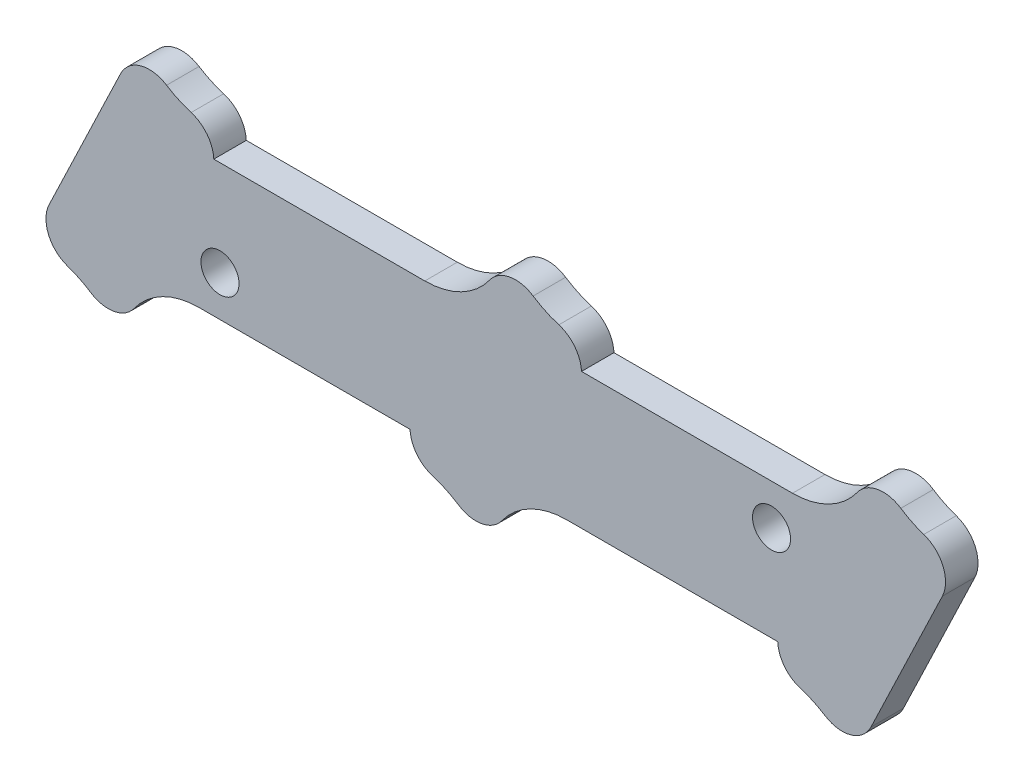
SolidWorks part; units mm, degrees
material "3003-H14"
ref_plane "X-Y Datum" through (0, 0, 0) normal (0, 0, 1) x (1, 0, 0)
ref_plane "X-Z Datum" through (0, 0, 0) normal (0, 1, 0) x (1, 0, 0)
ref_plane "Y-Z Datum" through (0, 0, 0) normal (1, 0, 0) x (0, 0, -1)
sketch "Sketch3" plane through (0, 0, 0) normal (0, 0, 1) x (1, 0, 0)
  line L0 (10.775, 10.775) -> (22.275, 34.775) construction
  line L1 (0, 0) -> (156.4633, 0) construction
  line L2 (0, 0) -> (0, 56.3098) construction
  line L3 (0, 56.3098) -> (156.4633, 56.3098) construction
  line L4 (156.4633, 0) -> (156.4633, 56.3098) construction
  line L5 (33.775, 10.775) -> (45.275, 34.775) construction
  line L6 (56.775, 10.775) -> (68.275, 34.775) construction
  line L7 (16.525, 22.775) -> (62.525, 22.775) construction
  line L8 (33.775, 10.775) -> (22.275, 34.775) construction
  line L9 (45.275, 34.775) -> (56.775, 10.775) construction
  line L10 (10.775, 10.775) -> (33.775, 10.775) construction
  line L11 (56.775, 10.775) -> (33.775, 10.775) construction
  line L12 (22.275, 34.775) -> (45.275, 34.775) construction
  line L13 (68.275, 34.775) -> (45.275, 34.775) construction
  line L14 (22.275, 34.775) -> (22.275, 10.775) construction
  line L15 (45.275, 10.775) -> (45.275, 34.775) construction
  line L16 (33.775, 10.775) -> (33.775, 34.775) construction
  line L17 (56.775, 34.775) -> (56.775, 10.775) construction
  line L18 (13.4804, 9.4786) -> (24.9804, 33.4786)
  line L19 (36.4804, 9.4786) -> (47.9804, 33.4786)
  line L20 (59.4804, 9.4786) -> (70.9804, 33.4786)
  line L21 (8.0696, 12.0714) -> (19.5696, 36.0714)
  line L22 (31.0696, 12.0714) -> (42.5696, 36.0714)
  line L23 (54.0696, 12.0714) -> (65.5696, 36.0714)
  line L24 (17.8152, 18.525) -> (57.1619, 18.525)
  line L25 (21.8881, 27.025) -> (61.2348, 27.025)
  line L26 (16.525, 27.025) -> (62.525, 27.025) construction
  line L27 (16.525, 18.525) -> (62.525, 18.525) construction
  line L48 (56.775, 10.775) -> (68.275, 10.775) construction
  line L49 (68.275, 10.775) -> (68.275, 34.775) construction
  circle A0 centre (10.775, 10.775) radius 10.775 construction
  circle A1 centre (33.775, 10.775) radius 10.775 construction
  circle A2 centre (22.275, 34.775) radius 10.775 construction
  circle A3 centre (45.275, 34.775) radius 10.775 construction
  circle A4 centre (68.275, 34.775) radius 10.775 construction
  circle A5 centre (56.775, 10.775) radius 10.775 construction
  circle A6 centre (10.775, 10.775) radius 4.7 construction
  circle A7 centre (33.775, 10.775) radius 4.7 construction
  circle A8 centre (56.775, 10.775) radius 4.7 construction
  circle A9 centre (68.275, 34.775) radius 4.7 construction
  circle A10 centre (45.275, 34.775) radius 4.7 construction
  circle A11 centre (22.275, 34.775) radius 4.7 construction
  circle A12 centre (22.275, 34.775) radius 6.2
  circle A13 centre (10.775, 10.775) radius 6.2
  circle A14 centre (33.775, 10.775) radius 6.2
  circle A15 centre (45.275, 34.775) radius 6.2
  circle A16 centre (68.275, 34.775) radius 6.2
  circle A17 centre (56.775, 10.775) radius 6.2
  circle A18 centre (125.775, 10.775) radius 10.775 construction
  circle A19 centre (102.775, 10.775) radius 10.775 construction
  circle A20 centre (79.775, 10.775) radius 10.775 construction
  circle A21 centre (91.275, 34.775) radius 10.775 construction
  circle A22 centre (114.275, 34.775) radius 10.775 construction
  circle A23 centre (137.275, 34.775) radius 10.775 construction
  dimension "D1" = 21.55
  dimension "D9" = 9.4
  dimension "D2" = 23
  dimension "D3" = 24
  dimension "D4" = 11.5
  dimension "D6" = 23
  dimension "D8" = 23
  dimension "D10" = 3
  dimension "D11" = 3
  dimension "D12" = 4.25
  dimension "D13" = 4.25
  dimension "D14" = 1.5
  dimension "D5" = 6
  dimension "D7" = 5
extrude "Boss-Extrude1" add sketch "Sketch3" along normal blind 2.032 contours L17 | L17 | L17 | L17 | L49 | A13 L18 A12 L21 | L25 L18 L24 L22 | L25 L22 L24 L19 | L25 L19 L24 L23 | A17 L20 A16 L23 | A14 L19 L24 L22 | A15 L22 L25 L19 region at (16.525, 22.775, 0) region at (28.025, 22.775, 0) region at (37.4592, 17.206, 0) region at (39.525, 22.775, 0) region at (41.5908, 28.344, 0) region at (51.025, 22.775, 0) region at (62.525, 22.775, 0)
ref_plane "Plane1" through (68.275, 0, 0) normal (1, 0, 0) x (0, 0, -1)
fillet "Fillet1" radius 5 4 edges at (61.2348, 27.025, 1.016) (38.2348, 27.025, 1.016) (40.8152, 18.525, 1.016) (17.8152, 18.525, 1.016)
fillet "Fillet4" radius 2 12 edges at (61.8251, 14.3718, 1.016) (56.4142, 16.9645, 1.016) (68.6358, 28.5855, 1.016) (63.2249, 31.1782, 1.016) (45.6358, 28.5855, 1.016) (40.2249, 31.1782, 1.016) (33.4142, 16.9645, 1.016) (38.8251, 14.3718, 1.016) (15.8251, 14.3718, 1.016) (10.4142, 16.9645, 1.016) (22.6358, 28.5855, 1.016) (17.2249, 31.1782, 1.016)
sketch "Sketch5" plane through (0, 0, 2.032) normal (0, 0, 1) x (1, 0, 0)
  line L0 (65.2304, 21.065) -> (12.379, 21.065) construction
  line L2 (11.5865, 19.4111) -> (16.0526, 28.7317) construction
  line L3 (13.898, 24.485) -> (66.4728, 24.485) construction
  line L4 (44.8881, 27.025) -> (58.0863, 27.025) construction
  line L5 (20.9637, 18.525) -> (34.1619, 18.525) construction
  line L6 (56.775, 10.775) -> (68.275, 34.775) construction
  line L7 (68.275, 34.775) -> (45.275, 34.775) construction
  line L8 (45.275, 34.775) -> (56.775, 10.775) construction
  line L9 (56.775, 34.775) -> (56.775, 10.775) construction
  line L10 (33.775, 10.775) -> (22.275, 34.775) construction
  line L11 (22.275, 34.775) -> (10.775, 10.775) construction
  line L12 (10.775, 10.775) -> (33.775, 10.775) construction
  line L13 (22.275, 10.775) -> (22.275, 34.775) construction
  circle A0 centre (33.775, 24.485) radius 1.1906
  circle A1 centre (22.275, 21.065) radius 1.1906
  circle A2 centre (56.775, 24.485) radius 1.1906
  circle A3 centre (45.275, 21.065) radius 1.1906
  point P19 (56.775, 24.485)
  dimension "D1" = 2.3813
  dimension "D2" = 2.54
  dimension "D3" = 2.54
extrude "Cut-Extrude1" cut sketch "Sketch5" against normal through all contours A1 | A2 region at (22.275, 21.065, 2.032) region at (56.775, 24.485, 2.032)
